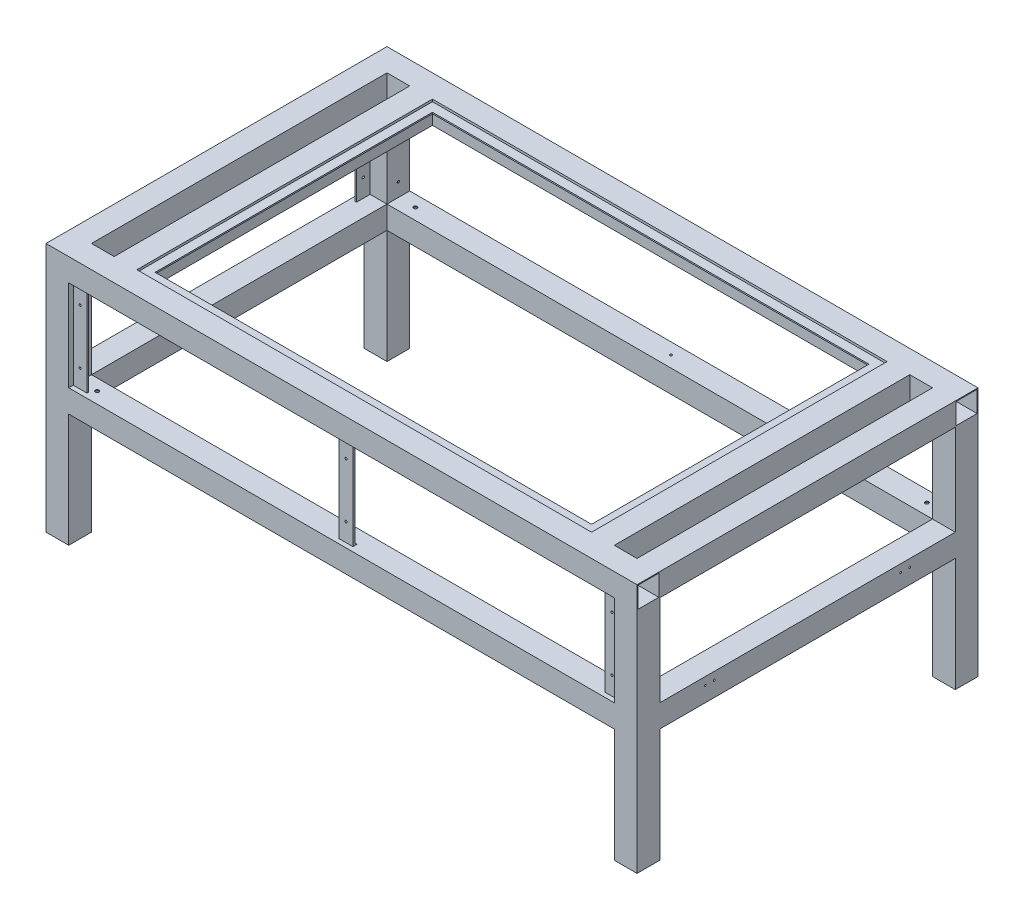
SolidWorks part; units mm, degrees
ref_plane "Plan de face" through (0, 0, 0) normal (0, 0, 1) x (1, 0, 0)
ref_plane "Plan de dessus" through (0, 0, 0) normal (0, 1, 0) x (1, 0, 0)
ref_plane "Plan de droite" through (0, 0, 0) normal (1, 0, 0) x (0, 0, -1)
sketch "Esquisse1" plane through (0, 0, 0) normal (0, 1, 0) x (1, 0, 0)
  line L1 (0, 0) -> (1300, 0)
  line L2 (0, 0) -> (0, 750)
  line L3 (0, 750) -> (1300, 750)
  line L4 (1300, 0) -> (1300, 750)
  line L5 (50, 700) -> (1250, 700)
  line L6 (50, 700) -> (50, 50)
  line L7 (50, 50) -> (1250, 50)
  line L8 (1250, 700) -> (1250, 50)
  dimension "D1" = 1300
  dimension "D2" = 750
  dimension "D3" = 50
  dimension "D4" = 50
  dimension "D5" = 50
  dimension "D6" = 50
extrude "Boss.-Extru.1" add sketch "Esquisse1" against normal blind 550
sketch "Esquisse2" plane through (0, 0, 0) normal (0, 0, 1) x (1, 0, 0)
  line L0 (0, 0) -> (1300, 0) construction
  line L1 (50, -50) -> (1250, -50)
  line L2 (50, -50) -> (50, -250)
  line L3 (50, -250) -> (1250, -250)
  line L4 (1250, -50) -> (1250, -250)
  line L5 (50, -300) -> (1250, -300)
  line L6 (50, -300) -> (50, -550)
  line L7 (50, -550) -> (1250, -550)
  line L8 (1250, -300) -> (1250, -550)
  line L9 (0, -550) -> (1300, -550) construction
  line L10 (1300, -550) -> (1300, 0) construction
  line L11 (0, -550) -> (0, 0) construction
  point P12 (1250, -425)
  dimension "D1" = 50
  dimension "D2" = 50
  dimension "D3" = 200
  dimension "D4" = 0
  dimension "D5" = 50
  dimension "D6" = 50
  dimension "D7" = 50
  dimension "D8" = 50
extrude "Enlèv. mat.-Extru.1" cut sketch "Esquisse2" against normal through all
sketch "Esquisse3" plane through (0, 0, 0) normal (-1, 0, 0) x (0, 0, 1)
  line L0 (-750, -550) -> (0, -550) construction
  line L1 (-700, -50) -> (-50, -50)
  line L2 (-700, -50) -> (-700, -250)
  line L3 (-700, -250) -> (-50, -250)
  line L4 (-50, -50) -> (-50, -250)
  line L5 (-700, -300) -> (-50, -300)
  line L6 (-700, -300) -> (-700, -550)
  line L7 (-700, -550) -> (-50, -550)
  line L8 (-50, -300) -> (-50, -550)
  line L9 (-750, 0) -> (0, 0) construction
  line L10 (0, -550) -> (0, 0) construction
  line L11 (-750, -550) -> (-750, 0) construction
  dimension "D1" = 50
  dimension "D2" = 50
  dimension "D3" = 50
  dimension "D4" = 50
  dimension "D5" = 50
  dimension "D6" = 200
  dimension "D7" = 50
extrude "Enlèv. mat.-Extru.2" cut sketch "Esquisse3" against normal through all
sketch "Esquisse4" plane through (0, 0, 0) normal (0, 1, 0) x (1, 0, 0)
  line L0 (1250, 700) -> (50, 700) construction
  line L1 (100, 700) -> (150, 700)
  line L2 (100, 700) -> (100, 50)
  line L3 (100, 50) -> (150, 50)
  line L4 (150, 700) -> (150, 50)
  line L5 (50, 50) -> (1250, 50) construction
  line L6 (50, 700) -> (50, 50) construction
  line L7 (1150, 700) -> (1200, 700)
  line L8 (1150, 700) -> (1150, 50)
  line L9 (1150, 50) -> (1200, 50)
  line L10 (1200, 700) -> (1200, 50)
  line L11 (1250, 50) -> (1250, 700) construction
  dimension "D1" = 50
  dimension "D2" = 50
  dimension "D3" = 50
  dimension "D4" = 50
extrude "Boss.-Extru.2" add sketch "Esquisse4" against normal blind 50 separate body
sketch "Esquisse18" plane through (0, -250, 0) normal (0, 1, 0) x (1, 0, 0)
  line L0 (50, 0) -> (1250, 0) construction
  line L1 (50, 750) -> (1250, 750) construction
  line L2 (1250, 750) -> (1250, 700) construction
  line L3 (50, 750) -> (50, 700) construction
  line L4 (1250, 50) -> (1250, 0) construction
  line L5 (50, 50) -> (50, 0) construction
  circle A0 centre (1212.5, 25) radius 4
  circle A1 centre (87.5, 25) radius 4
  circle A2 centre (87.5, 725) radius 4
  circle A3 centre (1212.5, 725) radius 4
  dimension "D1" = 8
  dimension "D2" = 8
  dimension "D3" = 8
  dimension "D4" = 8
  dimension "D5" = 1125
  dimension "D6" = 1125
  dimension "D7" = 25
  dimension "D8" = 25
  dimension "D9" = 25
  dimension "D10" = 25
  dimension "D11" = 700
  dimension "D12" = 700
  dimension "D13" = 37.5
  dimension "D14" = 37.5
  dimension "D15" = 37.5
  dimension "D16" = 37.5
extrude "Enlèv. mat.-Extru.5" cut sketch "Esquisse18" against normal blind 80
sketch "Esquisse19" plane through (0, -300, 0) normal (0, -1, 0) x (-1, 0, 0)
  circle A0 centre (-1212.5, 725) radius 15
  circle A1 centre (-87.5, 725) radius 15
  circle A2 centre (-87.5, 25) radius 15
  circle A3 centre (-1212.5, 25) radius 15
  dimension "D1" = 30
  dimension "D2" = 30
  dimension "D3" = 30
  dimension "D4" = 30
extrude "Enlèv. mat.-Extru.6" cut sketch "Esquisse19" against normal blind 48
sketch "Esquisse20" plane through (0, 0, 0) normal (-1, 0, 0) x (0, 0, 1)
  line L0 (-750, 0) -> (0, 0) construction
  line L1 (-2, -2) -> (-48, -2)
  line L2 (-2, -2) -> (-2, -48)
  line L3 (-2, -48) -> (-48, -48)
  line L4 (-48, -2) -> (-48, -48)
  line L5 (-702, -2) -> (-748, -2)
  line L6 (-702, -2) -> (-702, -48)
  line L7 (-702, -48) -> (-748, -48)
  line L8 (-748, -2) -> (-748, -48)
  line L9 (-750, -550) -> (-750, 0) construction
  line L10 (0, -550) -> (0, 0) construction
  dimension "D1" = 2
  dimension "D2" = 2
  dimension "D3" = 46
  dimension "D4" = 46
  dimension "D5" = 2
  dimension "D6" = 46
  dimension "D7" = 46
  dimension "D8" = 2
extrude "Enlèv. mat.-Extru.7" cut sketch "Esquisse20" against normal blind 10000
sketch "Esquisse21" plane through (0, -550, 0) normal (0, -1, 0) x (-1, 0, 0)
  line L0 (0, 0) -> (-50, 0) construction
  line L1 (-1252, 2) -> (-1298, 2)
  line L2 (-1252, 2) -> (-1252, 48)
  line L3 (-1252, 48) -> (-1298, 48)
  line L4 (-1298, 2) -> (-1298, 48)
  line L5 (-1252, 702) -> (-1298, 702)
  line L6 (-1252, 702) -> (-1252, 748)
  line L7 (-1252, 748) -> (-1298, 748)
  line L8 (-1298, 702) -> (-1298, 748)
  line L9 (-2, 702) -> (-48, 702)
  line L10 (-2, 702) -> (-2, 748)
  line L11 (-2, 748) -> (-48, 748)
  line L12 (-48, 702) -> (-48, 748)
  line L13 (-2, 2) -> (-48, 2)
  line L14 (-2, 2) -> (-2, 48)
  line L15 (-2, 48) -> (-48, 48)
  line L16 (-48, 2) -> (-48, 48)
  line L17 (-50, 50) -> (-50, 0) construction
  line L18 (-50, 50) -> (0, 50) construction
  line L19 (-50, 700) -> (0, 700) construction
  line L20 (-50, 750) -> (-50, 700) construction
  line L21 (-1300, 700) -> (-1250, 700) construction
  line L22 (-1300, 700) -> (-1300, 750) construction
  line L23 (-1250, 0) -> (-1300, 0) construction
  line L24 (-1300, 0) -> (-1300, 50) construction
  dimension "D1" = 46
  dimension "D2" = 2
  dimension "D3" = 2
  dimension "D4" = 2
  dimension "D5" = 46
  dimension "D6" = 46
  dimension "D7" = 2
  dimension "D8" = 2
  dimension "D9" = 46
  dimension "D10" = 46
  dimension "D11" = 2
  dimension "D12" = 2
  dimension "D13" = 46
  dimension "D14" = 46
  dimension "D15" = 2
  dimension "D16" = 2
extrude "Enlèv. mat.-Extru.8" cut sketch "Esquisse21" against normal blind 500
sketch "Esquisse22" plane through (0, 0, -50) normal (0, 0, -1) x (-1, 0, 0)
  line L0 (-50, -50) -> (0, -50) construction
  line L1 (-10, -50) -> (-40, -50)
  line L2 (-10, -50) -> (-10, -250)
  line L3 (-10, -250) -> (-40, -250)
  line L4 (-40, -50) -> (-40, -250)
  line L5 (-50, -250) -> (0, -250) construction
  line L6 (0, -250) -> (0, -50) construction
  dimension "D1" = 30
  dimension "D2" = 10
extrude "Boss.-Extru.11" add sketch "Esquisse22" along normal blind 3
sketch "Esquisse23" plane through (10, 0, 0) normal (-1, 0, 0) x (0, 0, 1)
  line L2 (-50, -250) -> (-80, -250)
  line L3 (-50, -250) -> (-50, -50)
  line L4 (-50, -50) -> (-80, -50)
  line L5 (-80, -250) -> (-80, -50)
  line L6 (-53, -50) -> (-50, -50) construction
  circle A0 centre (-65, -90) radius 2.5
  circle A1 centre (-65, -210) radius 2.5
  dimension "D2" = 5
  dimension "D3" = 5
  dimension "D1" = 30
  dimension "D4" = 0
  dimension "D5" = 15
  dimension "D6" = 15
  dimension "D7" = 40
  dimension "D8" = 40
extrude "Boss.-Extru.12" add sketch "Esquisse23" against normal blind 3
ref_plane "Plan1" through (0, 0, -375) normal (0, 0, 1) x (1, 0, 0)
ref_plane "Plan2" through (650, 0, 0) normal (-1, 0, 0) x (0, 0, 1)
ref_plane "Plan4" through (137.5, 0, 137.5) normal (0.7071, 0, 0.7071) x (0.7071, 0, -0.7071)
ref_plane "Plan5" through (0, 0, 0) normal (-0.7071, 0, -0.7071) x (-0.7071, 0, 0.7071)
mirror "Symétrie3" about plane through (0, 0, 0) normal (-0.7071, 0, -0.7071) of "Boss.-Extru.11", "Boss.-Extru.12"
sketch "Esquisse25" plane through (0, 0, -50) normal (0, 0, -1) x (-1, 0, 0)
  line L0 (-150, -50) -> (-150, 0) construction
  line L1 (-150, -5) -> (-1150, -5)
  line L2 (-150, -5) -> (-150, -25)
  line L3 (-150, -25) -> (-1150, -25)
  line L4 (-1150, -5) -> (-1150, -25)
  line L5 (-1150, -50) -> (-1150, 0) construction
  line L6 (-50, 0) -> (-1250, 0) construction
  dimension "D1" = 5
  dimension "D2" = 20
extrude "Boss.-Extru.14" add sketch "Esquisse25" along normal blind 3
sketch "Esquisse26" plane through (0, -5, 0) normal (0, 1, 0) x (1, 0, 0)
  line L0 (150, 50) -> (150, 700) construction
  line L1 (1150, 50) -> (150, 50)
  line L2 (1150, 50) -> (1150, 70)
  line L3 (1150, 70) -> (150, 70)
  line L4 (150, 50) -> (150, 70)
  dimension "D1" = 0
  dimension "D2" = 20
extrude "Boss.-Extru.15" add sketch "Esquisse26" against normal blind 3
mirror "Symétrie6" about plane through (0, 0, -375) normal (0, 0, 1) of "Boss.-Extru.15", "Boss.-Extru.14"
sketch "Esquisse27" plane through (1150, 0, 0) normal (-1, 0, 0) x (0, 0, 1)
  line L1 (-50, -5) -> (-700, -5)
  line L2 (-50, -5) -> (-50, -25)
  line L3 (-50, -25) -> (-700, -25)
  line L4 (-700, -5) -> (-700, -25)
extrude "Boss.-Extru.16" add sketch "Esquisse27" along normal blind 3
sketch "Esquisse28" plane through (0, -5, 0) normal (0, 1, 0) x (1, 0, 0)
  line L0 (150, 700) -> (1150, 700) construction
  line L1 (1150, 50) -> (1130, 50)
  line L2 (1150, 50) -> (1150, 700)
  line L3 (1150, 700) -> (1130, 700)
  line L4 (1130, 50) -> (1130, 700)
  dimension "D1" = 20
extrude "Boss.-Extru.17" add sketch "Esquisse28" against normal blind 3
mirror "Symétrie7" about plane through (650, 0, 0) normal (-1, 0, 0) of "Boss.-Extru.16", "Boss.-Extru.17"
sketch "Esquisse29" plane through (1250, 0, 0) normal (-1, 0, 0) x (0, 0, 1)
  line L0 (-750, -250) -> (-750, -50) construction
  line L1 (-750, -50) -> (-700, -50) construction
  line L2 (-750, -250) -> (-700, -250) construction
  circle A0 centre (-725, -220) radius 2.5
  circle A1 centre (-725, -80) radius 2.5
  dimension "D1" = 5
  dimension "D2" = 5
  dimension "D3" = 25
  dimension "D4" = 25
  dimension "D5" = 30
  dimension "D6" = 30
extrude "Enlèv. mat.-Extru.9" cut sketch "Esquisse29" against normal blind 10
mirror "Symétrie9" about plane through (650, 0, 0) normal (-1, 0, 0) of "Enlèv. mat.-Extru.9"
sketch "Esquisse30" plane through (0, -250, 0) normal (0, 1, 0) x (1, 0, 0)
  line L1 (50, 750) -> (1250, 750) construction
  line L2 (650, 302.5) -> (650, -302.5) construction
  circle A0 centre (650, 725) radius 2.5
  dimension "D1" = 5
  dimension "D2" = 25
  dimension "D3" = 0
extrude "Enlèv. mat.-Extru.10" cut sketch "Esquisse30" against normal blind 15
ref_plane "Plan6" through (0, -150, 0) normal (0, -1, 0) x (-1, 0, 0)
mirror "Symétrie10" about plane through (0, -150, 0) normal (0, -1, 0) of "Enlèv. mat.-Extru.10"
sketch "Esquisse31" plane through (0, -250, 0) normal (0, 1, 0) x (1, 0, 0)
  line L0 (50, 0) -> (1250, 0) construction
  line L1 (635, 15) -> (665, 15)
  line L2 (635, 15) -> (635, 10)
  line L3 (635, 10) -> (665, 10)
  line L4 (665, 15) -> (665, 10)
  line L5 (650, 302.5) -> (650, -302.5) construction
  point P6 (650, 10)
  dimension "D1" = 5
  dimension "D2" = 10
  dimension "D3" = 0
  dimension "D4" = 30
extrude "Boss.-Extru.18" add sketch "Esquisse31" along normal blind 200
fillet "Congé1" radius 5 2 edges at (650, -250, -15) (650, -50, -15)
sketch "Esquisse32" plane through (0, 0, -10) normal (0, 0, 1) x (1, 0, 0)
  line L0 (635, -250) -> (665, -250) construction
  line L1 (635, -50) -> (665, -50) construction
  line L2 (635, -50) -> (635, -250) construction
  circle A0 centre (650, -210) radius 2.5
  circle A1 centre (650, -90) radius 2.5
  dimension "D1" = 5
  dimension "D2" = 5
  dimension "D3" = 40
  dimension "D4" = 40
  dimension "D5" = 15
  dimension "D6" = 15
extrude "Enlèv. mat.-Extru.11" cut sketch "Esquisse32" against normal blind 5
mirror "Symétrie11" about plane through (0, 0, -375) normal (0, 0, 1) of "Boss.-Extru.12"
mirror "Symétrie15" about plane through (650, 0, 0) normal (-1, 0, 0) of "Symétrie3"
sketch "Esquisse33" plane through (1300, 0, 0) normal (1, 0, 0) x (0, 0, -1)
  line L0 (50, -50) -> (700, -50) construction
  line L1 (50, -250) -> (130.649, -250)
  line L2 (50, -250) -> (50, -50)
  line L3 (50, -50) -> (130.649, -50)
  line L4 (130.649, -250) -> (130.649, -50)
extrude "Enlèv. mat.-Extru.12" cut sketch "Esquisse33" against normal blind 78
sketch "Esquisse34" plane through (1300, 0, 0) normal (1, 0, 0) x (0, 0, -1)
  line L0 (50, -250) -> (50, -50) construction
  line L1 (700, -250) -> (50, -250) construction
  circle A0 centre (150, -267) radius 2
  circle A1 centre (170, -267) radius 2
  point P8 (0, 0)
  point P9 (0, 0)
  dimension "D2" = 4
  dimension "D3" = 4
  dimension "D1" = 20
  dimension "D4" = 100
  dimension "D5" = 17
  dimension "D6" = 17
extrude "Enlèv. mat.-Extru.13" cut sketch "Esquisse34" against normal blind 25
mirror "Symétrie16" about plane through (0, 0, -375) normal (0, 0, 1) of "Enlèv. mat.-Extru.13"
